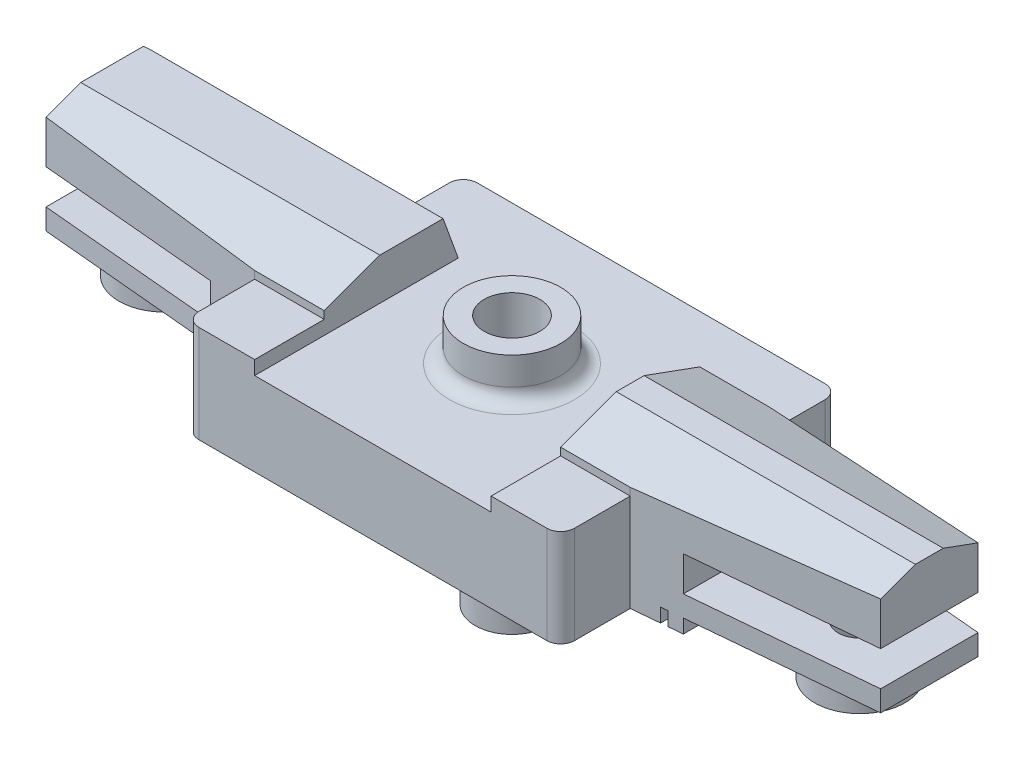
SolidWorks part; units mm, degrees
ref_plane "Front Plane" through (0, 0, 0) normal (0, 0, 1) x (1, 0, 0)
ref_plane "Top Plane" through (0, 0, 0) normal (0, 1, 0) x (1, 0, 0)
ref_plane "Right Plane" through (0, 0, 0) normal (1, 0, 0) x (0, 0, -1)
sketch "Sketch2" plane through (0, 0, 0) normal (0, 1, 0) x (1, 0, 0)
  line L1 (-15, 5) -> (15, 5)
  line L2 (-15, 5) -> (-15, -5)
  line L3 (-15, -5) -> (15, -5)
  line L4 (15, 5) -> (15, -5)
  line L5 (-15, 5) -> (15, -5) construction
  line L6 (-15, -5) -> (15, 5) construction
  circle A0 centre (0, 0) radius 1
  point P0 (0, 0)
  dimension "D3" = 2
  dimension "D1" = 30
  dimension "D2" = 10
extrude "Boss-Extrude1" add sketch "Sketch2" along normal blind 4.5
sketch "Sketch3" plane through (0, 4.5, 0) normal (0, 1, 0) x (1, 0, 0)
  line L0 (-15, -5) -> (15, -5) construction
  line L1 (-4.25, 5) -> (4.25, 5)
  line L2 (-4.25, 5) -> (-4.25, -5)
  line L3 (-4.25, -5) -> (4.25, -5)
  line L4 (4.25, 5) -> (4.25, -5)
  line L5 (-4.25, 5) -> (4.25, -5) construction
  line L6 (-4.25, -5) -> (4.25, 5) construction
  line L7 (15, 5) -> (-15, 5) construction
  line L8 (-4.25, 5) -> (-6.75, 5)
  line L9 (-4.25, 5) -> (-4.25, 2.5)
  line L10 (-4.25, 2.5) -> (-6.75, 2.5)
  line L11 (-6.75, 5) -> (-6.75, 2.5)
  line L12 (4.25, -5) -> (6.75, -5)
  line L13 (4.25, -5) -> (4.25, -2.5)
  line L14 (4.25, -2.5) -> (6.75, -2.5)
  line L15 (6.75, -5) -> (6.75, -2.5)
  line L16 (-15, -5) -> (15, -5)
  line L17 (15, 5) -> (-15, 5)
  line L19 (4.25, 5) -> (6.75, 5)
  line L20 (4.25, 5) -> (4.25, 2.5)
  line L21 (4.25, 2.5) -> (6.75, 2.5)
  line L22 (6.75, 5) -> (6.75, 2.5)
  circle A0 centre (0, 0) radius 1.75
  circle A1 centre (0, 0) radius 1 construction
  circle A2 centre (0, 0) radius 1
  point P0 (0, 0)
  line M14 (15, 5) -> (-15, 5)
  line M16 (-15, -5) -> (15, -5)
  circle M17 centre (0, 0) radius 1
  dimension "D3" = 3.5
  dimension "D1" = 8.5
  dimension "D2" = 2.5
extrude "Cut-Extrude1" cut sketch "Sketch3" against normal blind 1.5 contours L11 L10 L2 M14 | L22 L17 L4 L21 | L4 L2 A0 M14 M16 | M17 | L13 L12 L15 L14
sketch "Sketch4" plane through (0, 4.5, 0) normal (0, 1, 0) x (1, 0, 0)
  line L0 (15, -5) -> (15, 5) construction
  line L1 (-15, 1.75) -> (15, 1.75) construction
  line L2 (-15, 1.75) -> (-15, -1.75) construction
  line L3 (-15, -1.75) -> (15, -1.75) construction
  line L4 (15, 1.75) -> (15, -1.75) construction
  line L5 (-15, 1.75) -> (15, -1.75) construction
  line L6 (-15, -1.75) -> (15, 1.75) construction
  line L7 (-6.75, 5) -> (-6.75, 2.5)
  line L8 (-6.75, 2.5) -> (-15, 1.75)
  line L9 (-15, 1.75) -> (-15, 5)
  line L10 (-15, 5) -> (-6.75, 5)
  line L11 (6.75, -5) -> (6.75, -2.5)
  line L12 (6.75, -2.5) -> (15, -1.75)
  line L13 (15, -1.75) -> (15, -5)
  line L14 (15, -5) -> (6.75, -5)
  line L15 (15, 0) -> (-15, 0) construction
  line L16 (15, 5) -> (6.75, 5)
  line L17 (15, 1.75) -> (15, 5)
  line L18 (6.75, 2.5) -> (15, 1.75)
  line L19 (6.75, 5) -> (6.75, 2.5)
  line L20 (-15, -1.75) -> (-15, -5)
  line L21 (-6.75, -2.5) -> (-15, -1.75)
  line L22 (-6.75, -5) -> (-6.75, -2.5)
  line L23 (-15, -5) -> (-6.75, -5)
  circle A1 centre (0, 0) radius 1.75 construction
  point P0 (0, 0)
extrude "Cut-Extrude2" cut sketch "Sketch4" against normal through all contours L10 L7 L8 L9 | L16 L19 L18 L17 | L14 L11 L12 L13 | L20 L23 L22 L21
sketch "Sketch6" plane through (0, 0, 0) normal (0, 0, 1) x (1, 0, 0)
  line L0 (-6.75, 0) -> (-15, 0) construction
  line L1 (-7.75, 0) -> (-8, 0)
  line L2 (-7.75, 0) -> (-7.75, 0.5)
  line L3 (-7.75, 0.5) -> (-8, 0.5)
  line L4 (-8, 0) -> (-8, 0.5)
  line L5 (-15, 0) -> (-15, 4.5) construction
  line L6 (-8.5, 0) -> (-15, 0)
  line L7 (-8.5, 0) -> (-8.5, 0.5)
  line L8 (-8.5, 0.5) -> (-15, 0.5)
  line L9 (-15, 0) -> (-15, 0.5)
  line L10 (-6.75, 0) -> (-6.75, 4.5) construction
  line L11 (-15, 2.5) -> (-8.5, 2.5)
  line L12 (-15, 2.5) -> (-15, 1.25)
  line L13 (-15, 1.25) -> (-8.5, 1.25)
  line L14 (-8.5, 2.5) -> (-8.5, 1.25)
  dimension "D1" = 1
  dimension "D2" = 0.25
  dimension "D3" = 0.5
  dimension "D4" = 0.5
  dimension "D5" = 0.75
  dimension "D6" = 1.25
extrude "Cut-Extrude4" cut sketch "Sketch6" against normal mid plane 19
sketch "Sketch7" plane through (0, 0.5, 0) normal (0, -1, 0) x (1, 0, 0)
  circle A0 centre (-12.5, 0) radius 1.625
  circle A1 centre (-3, 3) radius 1
  circle A2 centre (-3, 3) radius 0.5
  circle A3 centre (-3, -3) radius 1
  circle A4 centre (-3, -3) radius 0.5
  dimension "D1" = 2
  dimension "D2" = 1
  dimension "D6" = 3.25
  dimension "D3" = 3
  dimension "D4" = 3
  dimension "D5" = 3
  dimension "D7" = 12.5
extrude "Boss-Extrude2" add sketch "Sketch7" along normal blind 1
hole_wizard "Ø1.55 (1.55) Diameter Hole2" positions "3DSketch2" profile "Sketch9" hole size "Ø1.55" standard "ANSI Metric"
sketch3d "3DSketch2"
  line L0 (-12.5, -0.5, 0) -> (-12.5, 0.5, 0) construction
  point P0 (-12.5, -0.5, 0)
sketch "Sketch9" plane through (-12.5, -0.5, 0) normal (1, 0, 0) x (0, 0, -1)
  line L0 (0, 0) -> (0, 3)
  line L1 (0, 3) -> (0.775, 2.5343)
  line L2 (0.775, 2.5343) -> (0.775, 0)
  line L5 (0.775, 0) -> (0, 0)
  line L10 (0, 3) -> (-0.775, 2.5343) construction
  line L11 (0, -6.35) -> (0, 107.95) construction
  dimension "Hole Dia." = 1.55
  dimension "Hole Depth" = 3
  dimension "Drill Angle" = 118
sketch "Sketch28" plane through (0, 3, 0) normal (0, 1, 0) x (1, 0, 0)
  line L16 (-6.75, 2.5) -> (-4.25, 2.5)
  line L17 (-4.25, 2.5) -> (-4.25, -5)
  line L18 (-4.25, -5) -> (6.75, -5)
  line L19 (6.75, -5) -> (6.75, -2.5)
  line L20 (6.75, -2.5) -> (4.25, -2.5)
  line L21 (4.25, -2.5) -> (4.25, 5)
  line L22 (4.25, 5) -> (-6.75, 5)
  line L23 (-6.75, 5) -> (-6.75, 2.5)
  circle A0 centre (-3, 3) radius 1
  circle A1 centre (-3, -3) radius 1
sketch "Sketch38" plane through (0, 3, 0) normal (0, 1, 0) x (1, 0, 0)
  line L1 (6.75, -5) -> (4.25, -5)
  line L2 (6.75, -5) -> (6.75, -2.5)
  line L3 (6.75, -2.5) -> (4.25, -2.5)
  line L4 (4.25, -5) -> (4.25, -2.5)
extrude "Boss-Extrude3" add sketch "Sketch38" along normal up to surface (1.5 mm away) up to face at (-8.3929, 4.5, 1.0714)
sketch "Sketch39" plane through (0, 4.5, 0) normal (0, 1, 0) x (1, 0, 0)
  line L1 (6.75, -2.5) -> (4.25, -2.5)
  line L2 (6.75, -2.5) -> (6.75, -5)
  line L3 (6.75, -5) -> (4.25, -5)
  line L4 (4.25, -2.5) -> (4.25, -5)
  line L5 (-6.75, -2.5) -> (-4.25, -2.5)
  line L6 (-6.75, -2.5) -> (-6.75, -5)
  line L7 (-6.75, -5) -> (-4.25, -5)
  line L8 (-4.25, -2.5) -> (-4.25, -5)
extrude "Cut-Extrude7" cut sketch "Sketch39" against normal blind 1
chamfer "Chamfer3" distance 2 angle 20 10 edges at (5.5, 4.5, 2.5) (-5.5, 4.5, 2.5) (-5.5, 4.5, -2.5) (-4.25, 3.75, -2.5) (-6.75, 3.75, -2.5) (-5.5, 3, -2.5) (5.5, 4.5, -2.5) (-10.875, 4.5, 2.125) (10.875, 4.5, 2.125) (10.875, 4.5, -2.125)
mirror "Mirror1" about plane through (0, 0, 0) normal (1, 0, 0) of "Cut-Extrude4", "Boss-Extrude2", "Ø1.55 (1.55) Diameter Hole2"
sketch "Sketch41" plane through (0, 0, 0) normal (0, -1, 0) x (1, 0, 0)
  circle A0 centre (0, 0) radius 1 construction
  circle A1 centre (0, 0) radius 1
extrude "Extrude-Thin1" add sketch "Sketch41" along normal blind 4.5 draft 1 thin
fillet "Fillet3" radius 0.5 5 edges at (-6.75, 1.5, -5) (-6.75, 1.75, 5) (6.75, 1.5, -5) (6.75, 1.75, 5) (0, 0, 1.4)
sketch "Sketch36" plane through (0, 0, 0) normal (0, -1, 0) x (1, 0, 0)
  line L0 (0, 1.5) -> (0, -1.5) construction
  line L1 (2, 1.5) -> (2, -1.5)
  line L2 (-2, 1.5) -> (-2, -1.5)
  arc A0 (2, 1.5) -> (-2, 1.5) centre (0, 1.5) ccw
  arc A1 (-2, -1.5) -> (2, -1.5) centre (0, -1.5) ccw
  point P3 (0, 0)
  dimension "D2" = 2
  dimension "D1" = 3
extrude "Cut-Extrude5" cut sketch "Sketch36" against normal blind 2
sketch "Sketch37" plane through (0, 0, 0) normal (1, 0, 0) x (0, 0, -1)
  line L0 (1.5, 2) -> (-1.5, 0) construction
  circle A0 centre (0, 1) radius 0.5
  dimension "D1" = 1
extrude "Cut-Extrude6" cut sketch "Sketch37" against normal mid plane 12
fillet "Fillet1" radius 0.5 1 edges at (0, 3, 1.75)
chamfer "Chamfer2" distance 0.5 distance2 0.5 1 edges at (0, 2, -1)
